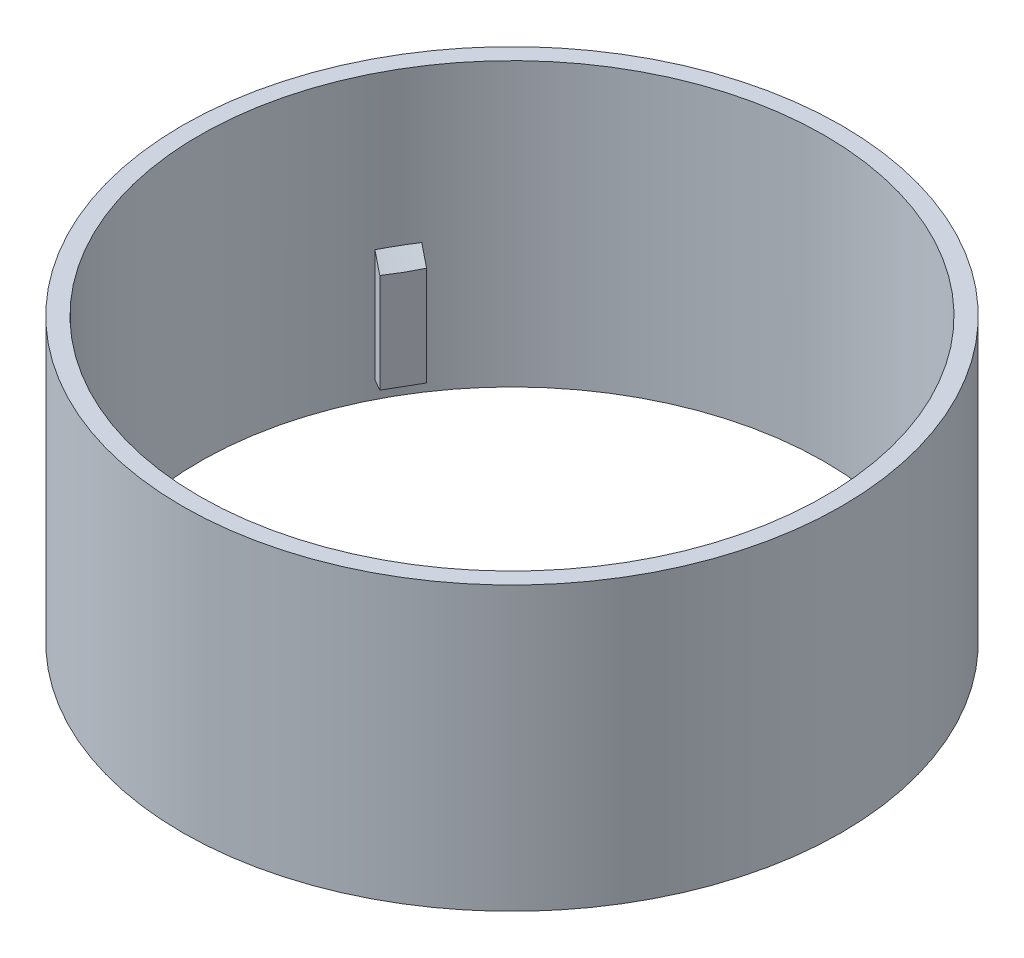
SolidWorks part; units mm, degrees
ref_plane "Спереди" through (0, 0, 0) normal (0, 0, 1) x (1, 0, 0)
ref_plane "Сверху" through (0, 0, 0) normal (0, 1, 0) x (1, 0, 0)
ref_plane "Справа" through (0, 0, 0) normal (1, 0, 0) x (0, 0, -1)
sketch "Эскиз1" plane through (0, 0, 0) normal (0, 1, 0) x (1, 0, 0)
  circle A0 centre (0, 0) radius 36.5
  circle A1 centre (0, 0) radius 38.5
  dimension "D1" = 73
  dimension "D2" = 2
extrude "Бобышка-Вытянуть1" add sketch "Эскиз1" along normal blind 40
ref_plane "Плоскость1" through (0, 0, 36.5) normal (0, 0, 1) x (1, 0, 0)
sketch "Эскиз2" plane through (0, 0, 36.5) normal (0, 0, 1) x (1, 0, 0)
  line L1 (1.95, 20.4471) -> (-0.95, 20.4471)
  line L2 (1.95, 20.4471) -> (1.95, 9)
  line L3 (1.95, 9) -> (-2.05, 9)
  line L4 (-2.05, 20.4471) -> (-2.05, 9)
  line L9 (-0.95, 20.4471) -> (-2.05, 20.4471)
  line L10 (-36.5, 0) -> (36.5, 0) construction
  point P0 (0, 15.7235)
  dimension "D1" = 4
  dimension "D2" = 11.4471
  dimension "D5" = 9
extrude "Бобышка-Вытянуть3" add sketch "Эскиз2" against normal blind 1.6
pattern_circular "Круговой массив1" count 3 over 360 about axis through (0, 0, 0) along (0, 1, 0) of "Бобышка-Вытянуть3"
sketch "Эскиз3" plane through (0, 0, 0) normal (0, -1, 0) x (1, 0, 0)
  circle A0 centre (0, 0) radius 52.9278
extrude "Вырез-Вытянуть1" cut sketch "Эскиз3" against normal blind 7
ref_plane "Плоскость2" through (0, 25.4471, 0) normal (0, 1, 0) x (1, 0, 0)
chamfer "Фаска1" distance 1.7 angle 45 12 edges at (-0.0501, 20.4471, 36.5) (-0.05, 20.4471, 34.9) (-2.05, 20.4471, 35.6712) (1.95, 20.4471, 35.6739) (-31.5849, 20.4471, -18.2933) (-29.8672, 20.4471, -19.6109) (-30.1993, 20.4471, -17.4933) (-31.8695, 20.4471, -16.1482) (31.6349, 20.4471, -18.2066) (31.9172, 20.4471, -16.0602) (30.2493, 20.4471, -17.4067) (29.9195, 20.4471, -19.5257)
